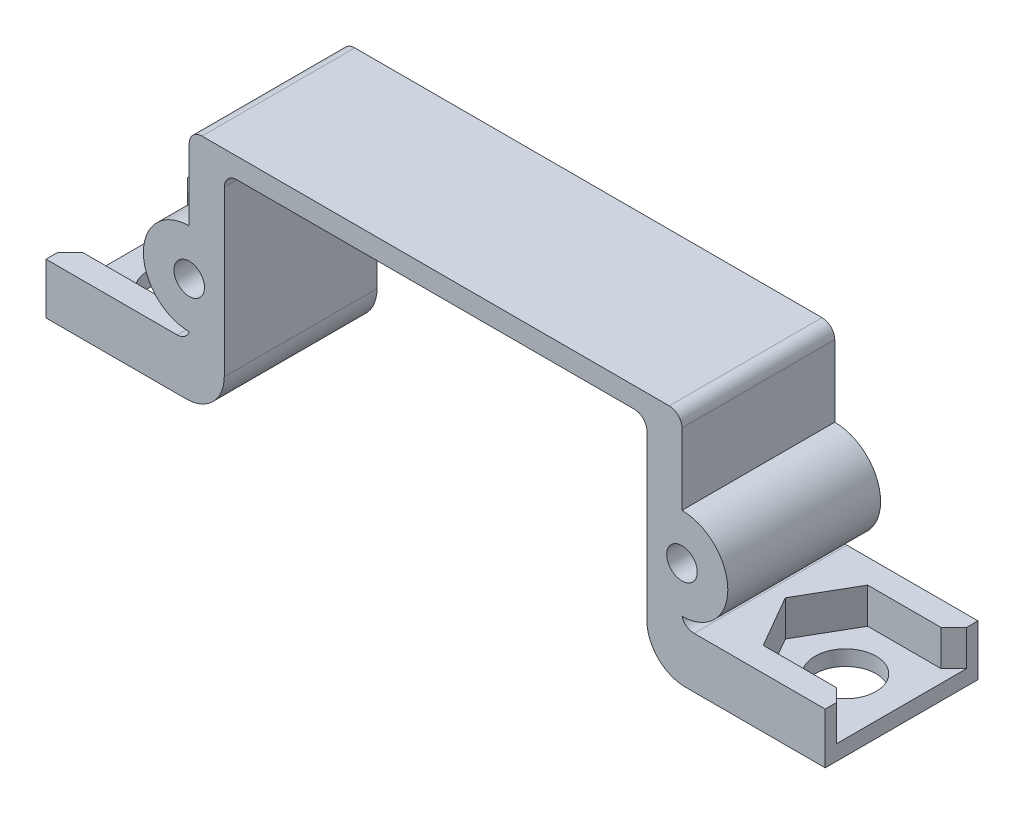
SolidWorks part; units mm, degrees
ref_plane "Front Plane" through (0, 0, 0) normal (0, 0, 1) x (1, 0, 0)
ref_plane "Top Plane" through (0, 0, 0) normal (0, 1, 0) x (1, 0, 0)
ref_plane "Right Plane" through (0, 0, 0) normal (1, 0, 0) x (0, 0, -1)
sketch "Sketch1" plane through (0, 0, 0) normal (0, 0, 1) x (1, 0, 0)
  line L0 (0, 0) -> (0, 4.145) construction
  line L1 (-8.3, 0) -> (-8.3, 8.45)
  line L2 (-8.3, 0) -> (-15.3, 0)
  line L3 (-15.3, 0) -> (-15.3, 2)
  line L4 (-15.3, 2) -> (-9.675, 2)
  line L5 (-8.3, 8.45) -> (8.3, 8.45)
  line L6 (-9.675, 2.345) -> (-9.675, 2)
  line L7 (-9.675, 5.945) -> (-9.675, 9.25)
  line L8 (-9.675, 9.25) -> (9.675, 9.25)
  line L10 (9.675, 5.945) -> (9.675, 9.25)
  line L11 (9.675, 2.345) -> (9.675, 2)
  line L12 (15.3, 2) -> (9.675, 2)
  line L13 (15.3, 0) -> (15.3, 2)
  line L14 (8.3, 0) -> (15.3, 0)
  line L15 (8.3, 0) -> (8.3, 8.45)
  circle A0 centre (-9.675, 4.145) radius 0.6
  arc A1 (-9.675, 5.945) -> (-9.675, 2.345) centre (-9.675, 4.145) ccw
  circle A2 centre (-9.675, 4.145) radius 1.8 construction
  arc A3 (9.675, 5.945) -> (9.675, 2.345) centre (9.675, 4.145) cw
  circle A4 centre (9.675, 4.145) radius 0.6
  dimension "D1" = 4.145
  dimension "D3" = 1.2
  dimension "D2" = 9.675
  dimension "D4" = 8.3
  dimension "D5" = 7
  dimension "D6" = 2
  dimension "D8" = 8.45
  dimension "D9" = 0.8
  dimension "D7" = 1.2
extrude "Boss-Extrude2" add sketch "Sketch1" against normal blind 5
sketch "Sketch2" plane through (0, 0, -5) normal (0, 0, -1) x (-1, 0, 0)
  line L14 (8.3, 0) -> (15.3, 0)
  line L15 (15.3, 0) -> (15.3, 2)
  line L16 (15.3, 2) -> (9.675, 2)
  line L17 (9.675, 2) -> (9.675, 2.345)
  line L18 (9.675, 5.945) -> (9.675, 9.25)
  line L19 (9.675, 9.25) -> (-9.675, 9.25)
  line L20 (-9.675, 9.25) -> (-9.675, 5.945)
  line L21 (-9.675, 2.345) -> (-9.675, 2)
  line L22 (-9.675, 2) -> (-15.3, 2)
  line L23 (-15.3, 2) -> (-15.3, 0)
  line L24 (-15.3, 0) -> (-8.3, 0)
  line L25 (-8.3, 0) -> (-8.3, 8.45)
  line L26 (-8.3, 8.45) -> (8.3, 8.45)
  line L27 (8.3, 8.45) -> (8.3, 0)
  line L28 (8.3, 0) -> (15.3, 0)
  line L29 (15.3, 0) -> (15.3, 2)
  line L30 (15.3, 2) -> (9.675, 2)
  line L31 (9.675, 2) -> (9.675, 2.345)
  line L32 (9.675, 2.345) -> (9.675, 9.25)
  line L33 (9.675, 9.25) -> (-9.675, 9.25)
  line L34 (-9.675, 9.25) -> (-9.675, 2.345)
  line L35 (-9.675, 2.345) -> (-9.675, 2)
  line L36 (-9.675, 2) -> (-15.3, 2)
  line L37 (-15.3, 2) -> (-15.3, 0)
  line L38 (-15.3, 0) -> (-8.3, 0)
  line L39 (-8.3, 0) -> (-8.3, 8.45)
  line L40 (-8.3, 8.45) -> (8.3, 8.45)
  line L41 (8.3, 8.45) -> (8.3, 0)
  arc A2 (9.675, 2.345) -> (9.675, 5.945) centre (9.675, 4.145) ccw
  arc A3 (-9.675, 5.945) -> (-9.675, 2.345) centre (-9.675, 4.145) ccw
  circle M17 centre (-9.675, 4.145) radius 0.6
  circle M18 centre (9.675, 4.145) radius 0.6
  line M19 (8.3, 0) -> (15.3, 0)
  line M20 (15.3, 0) -> (15.3, 2)
  line M21 (15.3, 2) -> (9.675, 2)
  line M22 (9.675, 2) -> (9.675, 2.345)
  arc M23 (9.675, 2.345) -> (9.675, 5.945) centre (9.675, 4.145) ccw
  line M24 (9.675, 5.945) -> (9.675, 9.25)
  line M25 (9.675, 9.25) -> (-9.675, 9.25)
  line M26 (-9.675, 9.25) -> (-9.675, 5.945)
  arc M27 (-9.675, 5.945) -> (-9.675, 2.345) centre (-9.675, 4.145) ccw
  line M28 (-9.675, 2.345) -> (-9.675, 2)
  line M29 (-9.675, 2) -> (-15.3, 2)
  line M30 (-15.3, 2) -> (-15.3, 0)
  line M31 (-15.3, 0) -> (-8.3, 0)
  line M32 (-8.3, 0) -> (-8.3, 8.45)
  line M33 (-8.3, 8.45) -> (8.3, 8.45)
  line M34 (8.3, 8.45) -> (8.3, 0)
  dimension "D1" = 0
extrude "Boss-Extrude3" add sketch "Sketch2" along normal blind 1 contours L32 M23 M18 | L34 L32 M26 M17 M28 M29 M30 M31 M32 M33 M34 M19 M20 M21 M22 M18 M24 M25 | L32 M18 | L32 M18 | L34 M27 M17 | L34 M17 | L34 M17 region at (-8.6197, 4.225, -5) region at (-10.5026, 4.145, -5) region at (-9.4204, 4.145, -5) region at (-9.9296, 4.145, -5) region at (10.5026, 4.145, -5) region at (9.9296, 4.145, -5) region at (9.4204, 4.145, -5)
sketch "Sketch4" plane through (0, 2, 0) normal (0, 1, 0) x (1, 0, 0)
  line L2 (15.3, 0.95) -> (11.9164, 0.95)
  line L4 (-15.3, 0.95) -> (-11.9164, 0.95)
  line L5 (-11.9164, 0.95) -> (-10.7329, 3)
  line L6 (-10.7329, 3) -> (-11.9164, 5.05)
  line L7 (-11.9164, 5.05) -> (-15.3, 5.05)
  line L9 (0, 0) -> (0, 6) construction
  line L11 (11.9164, 0.95) -> (10.7329, 3)
  line L12 (10.7329, 3) -> (11.9164, 5.05)
  line L13 (11.9164, 5.05) -> (15.3, 5.05)
  line L14 (-15.3, 0) -> (-9.675, 0)
  line L15 (-9.675, 0) -> (-9.675, 6)
  line L17 (-15.3, 6) -> (-15.3, 0)
  line L21 (-15.3, 5.05) -> (-15.3, 0.95)
  line L22 (-15.1725, 2.4897) -> (-14.5807, 1.4647) [skipped]
  line L23 (-13.6946, 6.0701) -> (-13.7459, 5.9812) [skipped]
  line L24 (15.3, 5.05) -> (15.3, 0.95)
  line L25 (-9.675, 6) -> (9.675, 6) construction
  line L28 (-9.675, 6) -> (-15.3, 6)
  arc A0 (-13.1, 0.95) -> (-13.1, 5.05) centre (-13.1, 3) ccw construction
  point P2 (0, 0)
  point P3 (0, 3)
  point P4 (13.1, 3)
  dimension "D1" = 4.1
  dimension "D2" = 0
  dimension "D3" = 2.2
extrude "Cut-Extrude2" cut sketch "Sketch4" against normal blind 1.4
chamfer "Chamfer1" distance 0.5 angle 45 4 edges at (15.3, 1.3, -0.95) (15.3, 1.3, -5.05) (-15.3, 1.3, -0.95) (-15.3, 1.3, -5.05)
hole_wizard "M2 Clearance Hole1" positions "Sketch6" profile "Sketch8" hole size "M2" standard "ANSI Metric" end condition through all
sketch "Sketch6" plane through (0, 2, 0) normal (0, 1, 0) x (1, 0, 0)
  point P0 (-13.1, 3)
  point P9 (13.1, 3)
sketch "Sketch8" plane through (-13.1, 2, -3) normal (1, 0, 0) x (0, 0, 1)
  line L0 (0, 0) -> (0, 2)
  line L1 (0, 2) -> (1.2, 2)
  line L2 (1.2, 2) -> (1.2, 0)
  line L5 (1.2, 0) -> (0, 0)
  line L11 (0, -6.35) -> (0, 107.95) construction
  dimension "Thru Hole Dia." = 2.4
  dimension "Thru Hole Depth" = 2
fillet "Fillet1" radius 1.5 2 edges at (8.3, 0, -3) (-8.3, 0, -3)
fillet "Fillet2" radius 0.5 2 edges at (-9.675, 2, -3) (9.675, 2, -3)
fillet "Fillet3" radius 0.5 4 edges at (8.3, 8.45, -3) (9.675, 9.25, -3) (-8.3, 8.45, -3) (-9.675, 9.25, -3)
